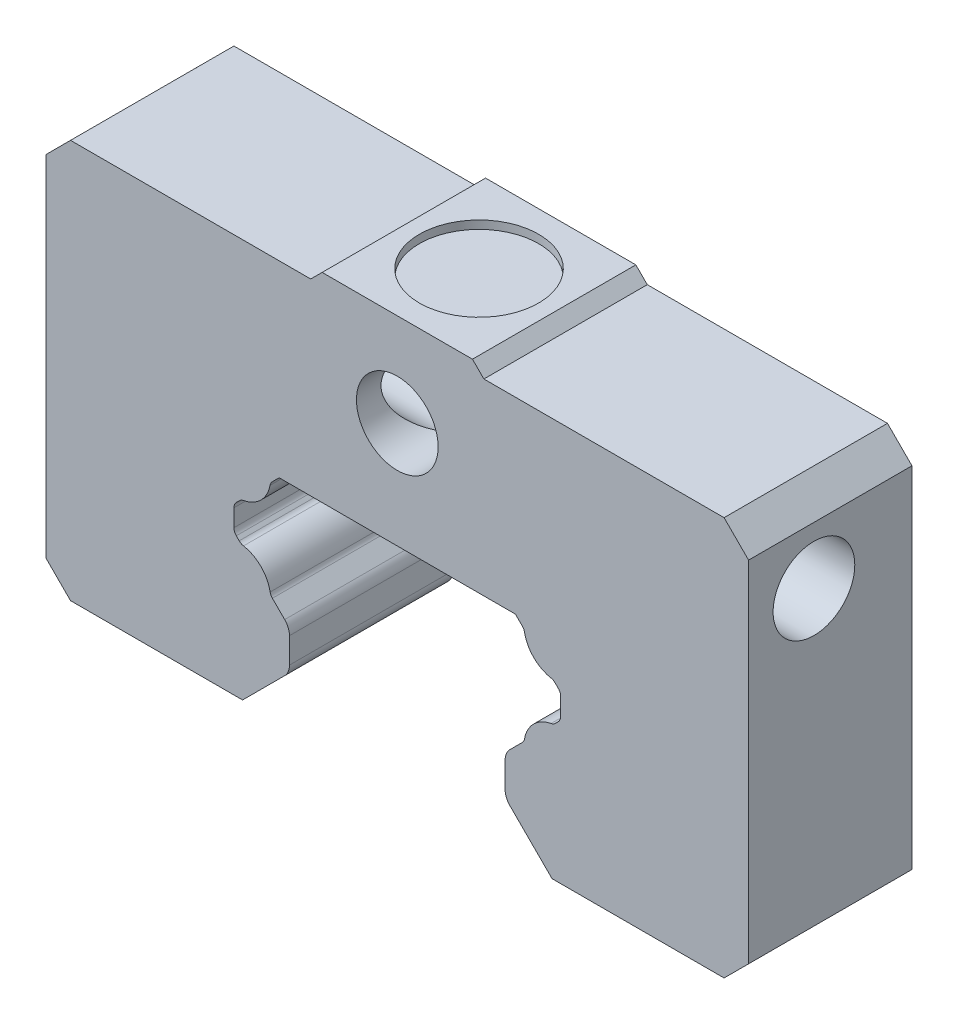
SolidWorks part; units mm, degrees
material "1060 Alloy"
ref_plane "Front Plane" through (0, 0, 0) normal (0, 0, 1) x (1, 0, 0)
ref_plane "Top Plane" through (0, 0, 0) normal (0, 1, 0) x (1, 0, 0)
ref_plane "Right Plane" through (0, 0, 0) normal (1, 0, 0) x (0, 0, -1)
sketch "Sketch3" plane through (0, 0, 0) normal (0, 0, 1) x (1, 0, 0)
  line L0 (-1000, 0) -> (49000, 0) construction
  line L1 (0, -1000) -> (0, 49000) construction
  line L2 (-7.2307, 12.9) -> (7.2307, 12.9)
  line L3 (-7.6477, 12.483) -> (-7.2307, 12.9)
  line L4 (-9.8536, 10.2772) -> (-9.6633, 10.4674)
  line L5 (-10, 8.8664) -> (-10, 9.9236)
  line L6 (-9.6753, 8.3346) -> (-9.8536, 8.5128)
  line L7 (-6.8929, 5.5522) -> (-7.6454, 6.3047)
  line L8 (-6.6, 3.2849) -> (-6.6, 4.8451)
  line L9 (-9.4707, 0) -> (-6.8929, 2.5778)
  line L10 (6.8929, 2.5778) -> (9.4707, 0)
  line L11 (6.6, 4.8451) -> (6.6, 3.2849)
  line L12 (7.6454, 6.3047) -> (6.8929, 5.5522)
  line L13 (9.8536, 8.5128) -> (9.6753, 8.3346)
  line L14 (10, 9.9236) -> (10, 8.8664)
  line L15 (9.6633, 10.4674) -> (9.8536, 10.2772)
  line L16 (7.2307, 12.9) -> (7.6477, 12.483)
  line L22 (5.3001, 24.4) -> (20.0001, 24.4)
  line L44 (19.9999, 0) -> (9.4707, 0)
  line L45 (21.5, 1.5) -> (19.9999, 0)
  line L46 (21.5, 22.9) -> (21.5, 1.5)
  line L47 (-21.5, 1.5) -> (-21.5, 22.8998)
  line L48 (-19.9999, 0) -> (-21.5, 1.5)
  line L49 (-9.4707, 0) -> (-19.9999, 0)
  line L64 (18.7501, 9.9) -> (18.7501, 14.9) construction
  line L65 (16.2501, 12.4) -> (21.2501, 12.4) construction
  line L66 (-18.7501, 9.9) -> (-18.7501, 14.9) construction
  line L67 (-21.2499, 12.4) -> (-16.2499, 12.4) construction
  line L989 (-5.2999, 24.4) -> (-4.5999, 25.1)
  line L990 (20.0001, 24.4) -> (21.5, 22.9)
  line L991 (-19.9999, 24.4) -> (-5.2999, 24.4)
  line L992 (-21.5, 22.8998) -> (-19.9999, 24.4)
  line L993 (4.6001, 25.1) -> (5.3001, 24.4)
  line L994 (-4.5999, 25.1) -> (4.6001, 25.1)
  arc A0 (-7.6477, 12.483) -> (-7.7854, 12.2224) centre (-7.2941, 12.1295) ccw
  arc A1 (-9.4027, 10.6051) -> (-7.7854, 12.2224) centre (-9.78, 12.5997) ccw
  arc A2 (-9.4027, 10.6051) -> (-9.6633, 10.4674) centre (-9.3098, 10.1138) ccw
  arc A3 (-9.8536, 10.2772) -> (-10, 9.9236) centre (-9.5, 9.9236) ccw
  arc A4 (-10, 8.8664) -> (-9.8536, 8.5128) centre (-9.5, 8.8664) ccw
  arc A5 (-9.6753, 8.3346) -> (-9.4124, 8.1964) centre (-9.3218, 8.6882) ccw
  arc A6 (-7.7836, 6.5677) -> (-9.4124, 8.1964) centre (-9.78, 6.2) ccw
  arc A7 (-7.7836, 6.5677) -> (-7.6454, 6.3047) centre (-7.2919, 6.6583) ccw
  arc A12 (-6.6, 4.8451) -> (-6.8929, 5.5522) centre (-7.6, 4.8451) ccw
  arc A13 (-6.8929, 2.5778) -> (-6.6, 3.2849) centre (-7.6, 3.2849) ccw
  arc A14 (6.6, 3.2849) -> (6.8929, 2.5778) centre (7.6, 3.2849) ccw
  arc A15 (6.8929, 5.5522) -> (6.6, 4.8451) centre (7.6, 4.8451) ccw
  arc A16 (7.6454, 6.3047) -> (7.7836, 6.5677) centre (7.2919, 6.6583) ccw
  arc A17 (9.4124, 8.1964) -> (9.6753, 8.3346) centre (9.3218, 8.6882) ccw
  arc A18 (9.4124, 8.1964) -> (7.7836, 6.5677) centre (9.78, 6.2) ccw
  arc A19 (9.8536, 8.5128) -> (10, 8.8664) centre (9.5, 8.8664) ccw
  arc A20 (10, 9.9236) -> (9.8536, 10.2772) centre (9.5, 9.9236) ccw
  arc A21 (9.6633, 10.4674) -> (9.4027, 10.6051) centre (9.3098, 10.1138) ccw
  arc A22 (7.7854, 12.2224) -> (9.4027, 10.6051) centre (9.78, 12.5997) ccw
  arc A23 (7.7854, 12.2224) -> (7.6477, 12.483) centre (7.2941, 12.1295) ccw
  dimension "D1" = 12.9
  dimension "D2" = 24.4
  dimension "D4" = 43
  dimension "D6" = 20
  dimension "D7" = 13.2
extrude "Endcap 1" add sketch "Sketch3" along normal blind 10 separate body
hole_wizard "Tap Drill for M6x1.0 Tap1" positions "Sketch6" profile "Sketch5" hole size "M6x1.0" standard "ANSI Metric"
sketch "Sketch6" plane through (0, 0, 10) normal (0, 0, 1) x (1, 0, 0)
  line L1 (20.0001, 24.4) -> (5.3001, 24.4) construction
  line L2 (0, -1000) -> (0, 49000) construction
  point P0 (0, 19.4)
  dimension "D1" = 5
sketch "Sketch5" plane through (0, 19.4, 10) normal (1, 0, 0) x (0, -1, 0)
  line L0 (0, 0) -> (0, 13.8014)
  line L1 (0, 13.8014) -> (2.5, 12.5)
  line L2 (2.5, 12.5) -> (2.5, 0)
  line L5 (2.5, 0) -> (0, 0)
  line L10 (0, 13.8014) -> (-2.5, 12.5) construction
  line L11 (0, -6.35) -> (0, 107.95) construction
  dimension "Hole Dia." = 5
  dimension "Hole Depth" = 12.5
  dimension "Drill Angle" = 125
cosmetic thread "Cosmetic Thread1" parameters "D1"=6, "D2"=6
hole_wizard "Tap Drill for M6x1.0 Tap2" positions "Sketch8" profile "Sketch7" hole size "M6x1.0" standard "ANSI Metric" end condition through all
sketch "Sketch8" plane through (21.5, 0, 0) normal (1, 0, 0) x (0, 0, -1)
  line L3 (-10, 24.4) -> (0, 24.4) construction
  line L5 (0, 1.5) -> (0, 22.9) construction
  point P0 (-6, 19.4)
  dimension "D1" = 5
  dimension "D2" = 6
sketch "Sketch7" plane through (21.5, 19.4, 6) normal (0, 1, 0) x (0, 0, -1)
  line L0 (0, 0) -> (0, 43)
  line L1 (0, 43) -> (2.5, 43)
  line L2 (2.5, 43) -> (2.5, 0)
  line L5 (2.5, 0) -> (0, 0)
  line L11 (0, -6.35) -> (0, 107.95) construction
  dimension "Thru Hole Dia." = 5
  dimension "Thru Hole Depth" = 43
cosmetic thread "Cosmetic Thread4" parameters "D1"=6, "D2"=6
cosmetic thread "Cosmetic Thread5" parameters "D1"=6, "D2"=6
sketch "Sketch9" plane through (0, 25.1, 0) normal (0, 1, 0) x (1, 0, 0)
  circle A0 centre (0.0001, -5) radius 3.65
  dimension "D1" = 7.3
extrude "Cut-Extrude1" cut sketch "Sketch9" against normal blind 0.5
